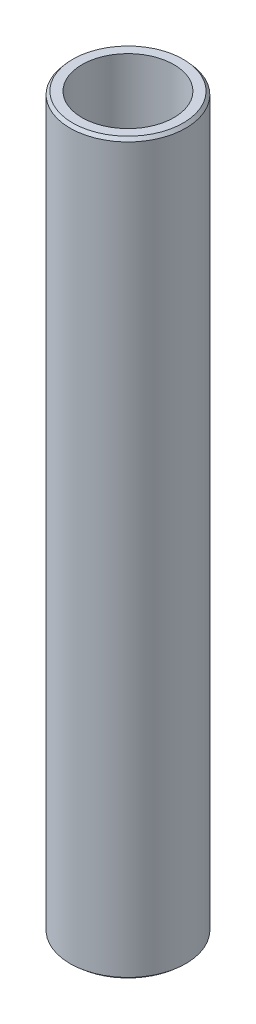
SolidWorks part; units mm, degrees
ref_plane "Front Plane" through (0, 0, 0) normal (0, 0, 1) x (1, 0, 0)
ref_plane "Top Plane" through (0, 0, 0) normal (0, 1, 0) x (1, 0, 0)
ref_plane "Right Plane" through (0, 0, 0) normal (1, 0, 0) x (0, 0, -1)
sketch "Sketch1" plane through (0, 0, 0) normal (0, 1, 0) x (1, 0, 0)
  circle A0 centre (0, 0) radius 40
  dimension "SHAFT_OD" = 80
extrude "Boss-Extrude1" add sketch "Sketch1" along normal blind 503.6592
sketch "Sketch2" plane through (0, 0, 0) normal (0, 1, 0) x (1, 0, 0)
  circle A0 centre (0, 0) radius 31.7389
  dimension "BORE_D" = 63.4779
extrude "Cut-Extrude1" cut sketch "Sketch2" along normal through all
chamfer "Chamfer1" distance 2.1436 angle 40.698 2 edges at (0, 503.6592, 40) (0, 0, 40) first distance on face at (0, 503.6592, 40) first distance on face at (0, 0, 31.7389)
